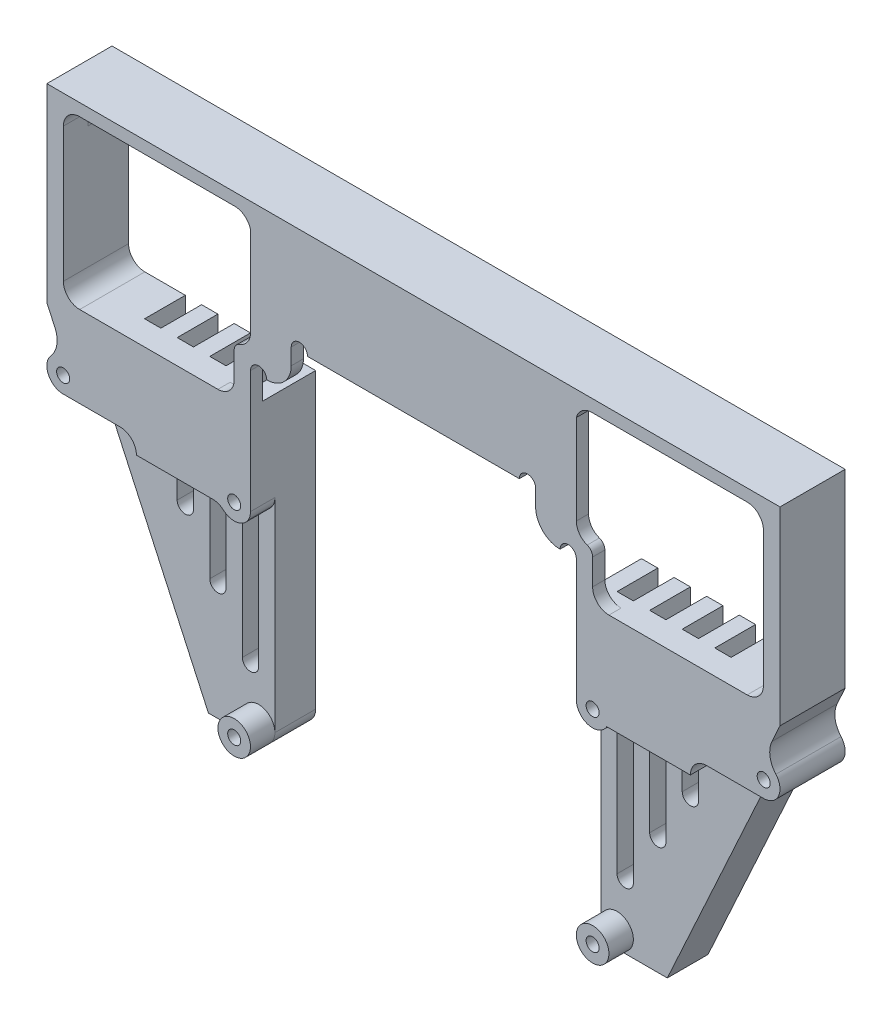
SolidWorks part; units mm, degrees
material "A2017"
ref_plane "正面" through (0, 0, 0) normal (0, 0, 1) x (1, 0, 0)
ref_plane "平面" through (0, 0, 0) normal (0, 1, 0) x (1, 0, 0)
ref_plane "右側面" through (0, 0, 0) normal (1, 0, 0) x (0, 0, -1)
sketch "ｽｹｯﾁ2" plane through (0, 0, 0) normal (0, 0, 1) x (1, 0, 0)
  line L0 (45, -77) -> (-45, -77)
  line L1 (-45, -77) -> (-45, -100.2724)
  line L2 (40.4547, -110.1895) -> (28.1283, -137.0833) construction
  line L3 (57.5, -85) -> (32.6737, -139.1665) construction
  line L4 (23.583, -145) -> (-23.583, -145) construction
  line L5 (-32.6737, -139.1665) -> (-57.5, -85) construction
  line L6 (45, -112.2727) -> (32.6737, -139.1665) construction
  line L7 (23.583, -145) -> (-23.583, -145) construction
  line L8 (-32.6737, -139.1665) -> (-45, -112.2727) construction
  line L9 (45, -77) -> (45, -100.2724)
  line L10 (45, -100.2724) -> (28.1665, -137)
  line L11 (-20, -80) -> (20, -80)
  line L12 (-28.1665, -137) -> (-45, -100.2724)
  line L13 (-28.1283, -137.0833) -> (-40.4547, -110.1895) construction
  line L15 (-20, -135) -> (-20, -80)
  line L19 (22, -137) -> (28.1665, -137)
  line L20 (-22, -137) -> (-28.1665, -137)
  line L22 (23.583, -140) -> (-23.583, -140) construction
  line L23 (20, -80) -> (20, -135.0066)
  line L24 (-43, -137) -> (-22, -137) construction
  line L25 (-20, -135) -> (-20, -79) construction
  line L26 (-45, -79) -> (-45, -135) construction
  line L27 (43, -77) -> (22, -77) construction
  line L28 (45, -135) -> (45, -79) construction
  line L29 (22, -137) -> (43, -137) construction
  line L30 (20, -79) -> (20, -135) construction
  arc A0 (23.583, -145) -> (32.6737, -139.1665) centre (23.583, -135) ccw construction
  arc A1 (-32.6737, -139.1665) -> (-23.583, -145) centre (-23.583, -135) ccw construction
  arc A2 (23.583, -145) -> (32.6737, -139.1665) centre (23.583, -135) ccw construction
  arc A3 (-32.6737, -139.1665) -> (-23.583, -145) centre (-23.583, -135) ccw construction
  arc A4 (-21.8257, -136.9924) -> (-20, -135) centre (-22, -135) ccw construction
  arc A5 (20.0076, -135.1743) -> (22, -137) centre (22, -135) ccw construction
  arc A8 (20, -135.0066) -> (22, -137) centre (22, -135) ccw
  arc A9 (-22, -137) -> (-20, -135) centre (-22, -135) ccw
  arc A10 (-28.1283, -137.0833) -> (-23.583, -140) centre (-23.583, -135) ccw construction
  arc A11 (23.583, -140) -> (28.1283, -137.0833) centre (23.583, -135) ccw construction
  dimension "D1" = 5
  dimension "D2" = 3
extrude "ﾎﾞｽ - 押し出し1" add sketch "ｽｹｯﾁ2" along normal blind 5
sketch "ｽｹｯﾁ3" plane through (0, 0, 5) normal (0, 0, 1) x (1, 0, 0)
  circle A0 centre (-43, -107) radius 2
  circle A1 centre (43, -107) radius 2
  circle A2 centre (43, -107) radius 1.25 construction
  dimension "D1" = 4
extrude "ﾎﾞｽ - 押し出し2" add sketch "ｽｹｯﾁ3" against normal up to surface (5 mm away) up to face at (0.0002, -111.1149, 0)
fillet "ﾌｨﾚｯﾄ1" radius 3 4 edges at (-42.8299, -105.0073, 2.5) (-41.3794, -108.172, 2.5) (41.3794, -108.172, 2.5) (42.8299, -105.0073, 2.5)
sketch "ｽｹｯﾁ4" plane through (0, 0, 5) normal (0, 0, 1) x (1, 0, 0)
  circle A0 centre (-43, -107) radius 2
  circle A1 centre (-22, -110) radius 2
  circle A2 centre (-22, -135) radius 2
  circle A3 centre (22, -135) radius 2
  circle A4 centre (22, -110) radius 2
  circle A5 centre (43, -107) radius 2
  dimension "D1" = 4
extrude "ﾎﾞｽ - 押し出し3" add sketch "ｽｹｯﾁ4" along normal blind 3
sketch "ｽｹｯﾁ5" plane through (0, 0, 5) normal (0, 0, 1) x (1, 0, 0)
  line L0 (20, -80) -> (20, -110) construction
  line L1 (20, -98.9998) -> (42.9701, -98.9998)
  line L2 (20, -98.9998) -> (20, -108.9998)
  line L3 (34, -108.9998) -> (42.9701, -108.9998)
  line L4 (42.9701, -98.9998) -> (42.9701, -108.9998)
  line L5 (20, -110) -> (20, -135) construction
  line L6 (20, -110.9998) -> (34, -110.9998)
  line L7 (20, -110.9998) -> (20, -108.9998)
  line L8 (0, -77) -> (0, -134.0805) construction
  line L9 (34, -110.9998) -> (34, -108.9998)
  line L10 (45, -77) -> (-45, -77) construction
  line L11 (-34, -110.9998) -> (-34, -108.9998)
  line L12 (-20, -110.9998) -> (-20, -108.9998)
  line L13 (-20, -110.9998) -> (-34, -110.9998)
  line L14 (-42.9701, -98.9998) -> (-42.9701, -108.9998)
  line L15 (-34, -108.9998) -> (-42.9701, -108.9998)
  line L16 (-20, -98.9998) -> (-20, -108.9998)
  line L17 (-20, -98.9998) -> (-42.9701, -98.9998)
  circle A0 centre (43, -107) radius 2 construction
  arc A1 (42.9701, -108.9998) -> (40.198, -110.7495) centre (42.9252, -111.9994) ccw construction
  dimension "D1" = 10
  dimension "D2" = 14
  dimension "D3" = 2
extrude "ﾎﾞｽ - 押し出し4" add sketch "ｽｹｯﾁ5" along normal up to surface (3 mm away) up to face at (24, -110, 8)
sketch "ｽｹｯﾁ6" plane through (0, 0, 8) normal (0, 0, 1) x (1, 0, 0)
  line L0 (0, -77) -> (0, -111.4657) construction
  line L1 (42.9701, -98.9998) -> (37.9701, -98.9998)
  line L2 (42.9701, -98.9998) -> (42.9701, -103.9998)
  line L3 (42.9701, -103.9998) -> (37.9701, -103.9998)
  line L4 (37.9701, -98.9998) -> (37.9701, -103.9998)
  line L5 (45, -77) -> (-45, -77) construction
  line L6 (-37.9701, -98.9998) -> (-37.9701, -103.9998)
  line L7 (-42.9701, -103.9998) -> (-37.9701, -103.9998)
  line L8 (-42.9701, -98.9998) -> (-42.9701, -103.9998)
  line L9 (-42.9701, -98.9998) -> (-37.9701, -98.9998)
  dimension "D1" = 5
  dimension "D2" = 5
extrude "ｶｯﾄ - 押し出し1" cut sketch "ｽｹｯﾁ6" against normal up to surface (3 mm away) up to face at (0, -96.0349, 5)
sketch "ｽｹｯﾁ7" plane through (0, 0, 5) normal (0, 0, 1) x (1, 0, 0)
  line L0 (45, -100.2724) -> (45, -77) construction
  line L1 (44.0112, -102.4297) -> (45, -100.2724) construction
  line L2 (45, -100.2724) -> (45, -77)
  line L3 (44.0112, -102.4297) -> (45, -100.2724)
  line L4 (-45, -77) -> (-45, -100.2724) construction
  line L5 (-45, -100.2724) -> (-44.0112, -102.4297) construction
  line L6 (-45, -77) -> (-45, -100.2724)
  line L7 (-45, -100.2724) -> (-44.0112, -102.4297)
  line L8 (45, -77) -> (-45, -77) construction
  line L9 (45, -77) -> (-45, -77)
  line L10 (42.9701, -105.0002) -> (42.9701, -80)
  line L11 (42.9701, -80) -> (-42.9701, -80)
  line L12 (-42.9701, -80) -> (-42.9701, -105.0002)
  arc A0 (44.0112, -102.4297) -> (44.4954, -105.6719) centre (46.7384, -103.6797) ccw construction
  arc A1 (44.0112, -102.4297) -> (44.4954, -105.6719) centre (46.7384, -103.6797) ccw
  arc A2 (-44.4954, -105.6719) -> (-44.0112, -102.4297) centre (-46.7384, -103.6797) ccw construction
  arc A3 (-44.4954, -105.6719) -> (-44.0112, -102.4297) centre (-46.7384, -103.6797) ccw
  arc A5 (42.9701, -108.9998) -> (42.9701, -105.0002) centre (43, -107) ccw construction
  arc A6 (-42.9701, -105.0002) -> (-44.4954, -105.6719) centre (-43, -107) ccw construction
  arc A8 (44.4954, -105.6719) -> (42.9701, -105.0002) centre (43, -107) ccw
  arc A9 (-42.9701, -105.0002) -> (-44.4954, -105.6719) centre (-43, -107) ccw
extrude "ﾎﾞｽ - 押し出し5" add sketch "ｽｹｯﾁ7" along normal up to surface (3 mm away) up to face at (32.6255, -106.7271, 8)
sketch "ｽｹｯﾁ8" plane through (0, 0, 5) normal (0, 0, 1) x (1, 0, 0)
  line L0 (42.9701, -103.9998) -> (42.9701, -80) construction
  line L1 (42.9701, -80) -> (20, -80) construction
  line L2 (20, -80) -> (20, -98.9998) construction
  line L3 (20, -98.9998) -> (37.9701, -98.9998) construction
  line L4 (37.9701, -98.9998) -> (37.9701, -103.9998) construction
  line L5 (37.9701, -103.9998) -> (42.9701, -103.9998) construction
  line L6 (-20, -80) -> (-42.9701, -80) construction
  line L7 (-42.9701, -80) -> (-42.9701, -103.9998) construction
  line L8 (-42.9701, -103.9998) -> (-37.9701, -103.9998) construction
  line L9 (-37.9701, -103.9998) -> (-37.9701, -98.9998) construction
  line L10 (-37.9701, -98.9998) -> (-20, -98.9998) construction
  line L11 (-20, -98.9998) -> (-20, -80) construction
  line L12 (42.9701, -103.9998) -> (42.9701, -80)
  line L13 (42.9701, -80) -> (20, -80)
  line L14 (20, -80) -> (20, -98.9998)
  line L15 (20, -98.9998) -> (37.9701, -98.9998)
  line L16 (37.9701, -98.9998) -> (37.9701, -103.9998)
  line L17 (37.9701, -103.9998) -> (42.9701, -103.9998)
  line L18 (-20, -80) -> (-42.9701, -80)
  line L19 (-42.9701, -80) -> (-42.9701, -103.9998)
  line L20 (-42.9701, -103.9998) -> (-37.9701, -103.9998)
  line L21 (-37.9701, -103.9998) -> (-37.9701, -98.9998)
  line L22 (-37.9701, -98.9998) -> (-20, -98.9998)
  line L23 (-20, -98.9998) -> (-20, -80)
extrude "ｶｯﾄ - 押し出し2" cut sketch "ｽｹｯﾁ8" against normal through all
fillet "ﾌｨﾚｯﾄ2" radius 2 6 edges at (-42.9701, -103.9998, 4) (-37.9701, -103.9998, 4) (37.9701, -103.9998, 4) (42.9701, -103.9998, 4) (42.9701, -80, 4) (-42.9701, -80, 4)
sketch "ｽｹｯﾁ9" plane through (0, 0, 8) normal (0, 0, 1) x (1, 0, 0)
  line L0 (20, -77) -> (20, -82.5) construction
  line L1 (42.9701, -82) -> (20, -82)
  line L2 (42.9701, -82) -> (42.9701, -78.5)
  line L3 (42.9701, -78.5) -> (20, -78.5)
  line L4 (20, -82) -> (20, -78.5)
  line L5 (45, -77) -> (-45, -77) construction
  line L6 (0, -77) -> (0, -137.6393) construction
  line L7 (-20, -82) -> (-20, -78.5)
  line L8 (-42.9701, -78.5) -> (-20, -78.5)
  line L9 (-42.9701, -82) -> (-42.9701, -78.5)
  line L10 (-42.9701, -82) -> (-20, -82)
  dimension "D1" = 1.5
extrude "ｶｯﾄ - 押し出し3" cut sketch "ｽｹｯﾁ9" against normal blind 3
fillet "ﾌｨﾚｯﾄ3" radius 2 4 edges at (42.9701, -78.5, 6.5) (20, -78.5, 6.5) (-20, -78.5, 6.5) (-42.9701, -78.5, 6.5)
fillet "ﾌｨﾚｯﾄ4" radius 2 5 edges at (34, -108.9998, 6.5) (-20, -110.9998, 6.5) (20, -110.9998, 6.5) (-23.7322, -110.9998, 6.5) (-34, -108.9998, 6.5)
sketch "ｽｹｯﾁ10" plane through (0, 0, 0) normal (0, 0, -1) x (-1, 0, 0)
  line L0 (-23, -98.9998) -> (-23, -128.9998) construction
  line L1 (-20, -98.9998) -> (-37.9701, -98.9998) construction
  line L2 (-22, -98.9998) -> (-22, -128.9998)
  line L3 (-24, -98.9998) -> (-24, -128.9998)
  line L4 (-20, -98.9998) -> (-20, -135.0066) construction
  line L5 (-27, -98.9998) -> (-27, -122.6356) construction
  line L6 (-26, -98.9998) -> (-26, -122.6356)
  line L7 (-28, -98.9998) -> (-28, -122.6356)
  line L8 (-23, -128.9998) -> (-39.9701, -101.9998) construction
  line L9 (-31, -98.9998) -> (-31, -116.2715) construction
  line L10 (-30, -98.9998) -> (-30, -116.2715)
  line L11 (-32, -98.9998) -> (-32, -116.2715)
  line L12 (-35, -98.9998) -> (-35, -109.9073) construction
  line L13 (-34, -98.9998) -> (-34, -109.9073)
  line L14 (-36, -98.9998) -> (-36, -109.9073)
  line L15 (0, -77) -> (0, -136.588) construction
  line L16 (-45, -77) -> (45, -77) construction
  line L17 (23, -98.9998) -> (23, -128.9998) construction
  line L18 (22, -98.9998) -> (22, -128.9998)
  line L19 (24, -98.9998) -> (24, -128.9998)
  line L20 (27, -98.9998) -> (27, -122.6356) construction
  line L21 (26, -98.9998) -> (26, -122.6356)
  line L22 (28, -98.9998) -> (28, -122.6356)
  line L23 (31, -98.9998) -> (31, -116.2715) construction
  line L24 (30, -98.9998) -> (30, -116.2715)
  line L25 (32, -98.9998) -> (32, -116.2715)
  line L26 (35, -98.9998) -> (35, -109.9073) construction
  line L27 (34, -98.9998) -> (34, -109.9073)
  line L28 (36, -98.9998) -> (36, -109.9073)
  line L29 (23, -128.9998) -> (39.9701, -101.9998) construction
  arc A0 (-22, -98.9998) -> (-24, -98.9998) centre (-23, -98.9998) ccw
  arc A1 (-24, -128.9998) -> (-22, -128.9998) centre (-23, -128.9998) ccw
  arc A2 (-26, -98.9998) -> (-28, -98.9998) centre (-27, -98.9998) ccw
  arc A3 (-28, -122.6356) -> (-26, -122.6356) centre (-27, -122.6356) ccw
  arc A4 (-30, -98.9998) -> (-32, -98.9998) centre (-31, -98.9998) ccw
  arc A5 (-32, -116.2715) -> (-30, -116.2715) centre (-31, -116.2715) ccw
  arc A6 (-34, -98.9998) -> (-36, -98.9998) centre (-35, -98.9998) ccw
  arc A7 (-36, -109.9073) -> (-34, -109.9073) centre (-35, -109.9073) ccw
  arc A8 (22, -98.9998) -> (24, -98.9998) centre (23, -98.9998) cw
  arc A9 (24, -128.9998) -> (22, -128.9998) centre (23, -128.9998) cw
  arc A10 (26, -98.9998) -> (28, -98.9998) centre (27, -98.9998) cw
  arc A11 (28, -122.6356) -> (26, -122.6356) centre (27, -122.6356) cw
  arc A12 (30, -98.9998) -> (32, -98.9998) centre (31, -98.9998) cw
  arc A13 (32, -116.2715) -> (30, -116.2715) centre (31, -116.2715) cw
  arc A14 (34, -98.9998) -> (36, -98.9998) centre (35, -98.9998) cw
  arc A15 (36, -109.9073) -> (34, -109.9073) centre (35, -109.9073) cw
  point P4 (-23, -113.9998)
  point P13 (-27, -110.8177)
  point P23 (-31, -107.6356)
  point P30 (-35, -104.4536)
  point P42 (23, -113.9998)
  point P49 (27, -110.8177)
  point P56 (31, -107.6356)
  point P63 (35, -104.4536)
  dimension "D1" = 2
  dimension "D2" = 2
  dimension "D3" = 30
  dimension "D4" = 2
  dimension "D5" = 2
  dimension "D6" = 2
extrude "ｶｯﾄ - 押し出し4" cut sketch "ｽｹｯﾁ10" against normal blind 5
hole_wizard "M2 ねじ穴1" positions "ｽｹｯﾁ11" profile "ｽｹｯﾁ13" tap size "M2" standard "JIS" end condition through all
sketch "ｽｹｯﾁ11" plane through (0, 0, 8) normal (0, 0, 1) x (1, 0, 0)
  point P0 (43, -107)
  point P3 (22, -110)
  point P6 (22, -135)
  point P9 (-22, -110)
  point P12 (-22, -135)
  point P15 (-43, -107)
sketch "ｽｹｯﾁ13" plane through (43, -107, 8) normal (1, 0, 0) x (0, -1, 0)
  line L0 (0, 0) -> (0, 8)
  line L1 (0, 8) -> (0.8, 8)
  line L2 (0.8, 8) -> (0.8, 0)
  line L5 (0.8, 0) -> (0, 0)
  line L11 (0, -6.35) -> (0, 107.95) construction
  dimension "次ｻｰﾌｪｽまでのねじ下穴ﾄﾞﾘﾙ直径" = 1.6
  dimension "次ｻｰﾌｪｽまでのねじ下穴ﾄﾞﾘﾙの深さ" = 8
cosmetic thread "穴のねじ山1" parameters "D2"=2
cosmetic thread "穴のねじ山2" parameters "D2"=2
cosmetic thread "穴のねじ山3" parameters "D2"=2
cosmetic thread "穴のねじ山4" parameters "D2"=2
cosmetic thread "穴のねじ山5" parameters "D2"=2
cosmetic thread "穴のねじ山6" parameters "D2"=2
sketch "ｽｹｯﾁ14" plane through (0, 0, 8) normal (0, 0, 1) x (1, 0, 0)
  line L0 (-42.9701, -101.9998) -> (-42.9701, -80.5) construction
  line L1 (-40.9701, -103.9998) -> (-39.9701, -103.9998) construction
  line L2 (-37.9701, -101.9998) -> (-37.9701, -98.9998) construction
  line L3 (42.9701, -80.5) -> (42.9701, -101.9998) construction
  line L4 (39.9701, -103.9998) -> (40.9701, -103.9998) construction
  line L5 (37.9701, -98.9998) -> (37.9701, -101.9998) construction
  line L6 (-42.9701, -101.9998) -> (-42.9701, -98.9998)
  line L7 (-40.9701, -103.9998) -> (-39.9701, -103.9998)
  line L8 (-37.9701, -101.9998) -> (-37.9701, -98.9998)
  line L9 (42.9701, -98.9998) -> (42.9701, -101.9998)
  line L10 (39.9701, -103.9998) -> (40.9701, -103.9998)
  line L11 (37.9701, -98.9998) -> (37.9701, -101.9998)
  line L12 (37.9701, -98.9998) -> (42.9701, -98.9998)
  line L13 (-37.9701, -98.9998) -> (-42.9701, -98.9998)
  arc A0 (-42.9701, -101.9998) -> (-40.9701, -103.9998) centre (-40.9701, -101.9998) ccw construction
  arc A1 (-39.9701, -103.9998) -> (-37.9701, -101.9998) centre (-39.9701, -101.9998) ccw construction
  arc A2 (40.9701, -103.9998) -> (42.9701, -101.9998) centre (40.9701, -101.9998) ccw construction
  arc A3 (37.9701, -101.9998) -> (39.9701, -103.9998) centre (39.9701, -101.9998) ccw construction
  arc A4 (-42.9701, -101.9998) -> (-40.9701, -103.9998) centre (-40.9701, -101.9998) ccw
  arc A5 (-39.9701, -103.9998) -> (-37.9701, -101.9998) centre (-39.9701, -101.9998) ccw
  arc A6 (40.9701, -103.9998) -> (42.9701, -101.9998) centre (40.9701, -101.9998) ccw
  arc A7 (37.9701, -101.9998) -> (39.9701, -103.9998) centre (39.9701, -101.9998) ccw
extrude "ﾎﾞｽ - 押し出し6" add sketch "ｽｹｯﾁ14" against normal up to surface (8 mm away) up to face at (43.8, -107, 0)
fillet "ﾌｨﾚｯﾄ5" radius 2 2 edges at (-42.9701, -98.9998, 4) (42.9701, -98.9998, 4)
sketch "ｽｹｯﾁ15" plane through (0, 0, 8) normal (0, 0, 1) x (1, 0, 0)
  line L0 (-14.5, -90) -> (14.5, -90) construction
  line L1 (-20, -80) -> (20, -80)
  line L2 (-20, -80) -> (-20, -90)
  line L3 (-20, -90) -> (20, -90)
  line L4 (20, -80) -> (20, -90)
extrude "ﾎﾞｽ - 押し出し8" add sketch "ｽｹｯﾁ15" against normal blind 1.5
sketch "ｽｹｯﾁ16" plane through (0, 0, 8) normal (0, 0, 1) x (1, 0, 0)
  line L2 (20, -98.9998) -> (20, -95)
  line L3 (20, -95.5) -> (20, -93) construction
  line L4 (20, -95) -> (18, -95)
  line L5 (15, -92) -> (15, -90)
  line L6 (-20, -90) -> (20, -90) construction
  line L11 (20, -135) -> (20, -79) construction
  line L12 (20, -98.9998) -> (22, -98.9998) construction
  line L13 (20, -98.9998) -> (22, -98.9998)
  line L14 (22, -98.9998) -> (22, -93)
  line L15 (15, -90) -> (20, -90)
  line L16 (22, -93) -> (20, -93)
  line L17 (20, -93) -> (20, -90)
  arc A0 (15, -92) -> (18, -95) centre (18, -92) ccw construction
  arc A1 (15, -92) -> (18, -95) centre (18, -92) ccw
  dimension "D1" = 3
extrude "ﾎﾞｽ - 押し出し9" add sketch "ｽｹｯﾁ16" against normal up to surface (1.5 mm away) up to face at (0, -85, 6.5)
mirror "ﾐﾗｰ1" about plane through (0, 0, 0) normal (1, 0, 0) of "ﾎﾞｽ - 押し出し9"
fillet "ﾌｨﾚｯﾄ7" radius 2 2 edges at (-20, -93, 7.25) (20, -93, 7.25)
fillet "ﾌｨﾚｯﾄ8" radius 1 2 edges at (22, -93, 7.25) (-22, -93, 7.25)
fillet "ﾌｨﾚｯﾄ9" radius 2 2 edges at (22, -98.9998, 7.25) (-22, -98.9998, 7.25)
sketch "ｽｹｯﾁ17" plane through (0, 0, 8) normal (0, 0, 1) x (1, 0, 0)
  line L0 (-18, -95) -> (-20, -95) construction
  line L1 (-15, -90) -> (15, -90) construction
  line L2 (0, -77) -> (0, -99.7898) construction
  line L3 (45, -77) -> (-45, -77) construction
  circle A0 centre (-19, -95) radius 1
  circle A1 centre (-14, -90) radius 1
  circle A2 centre (14, -90) radius 1
  circle A3 centre (19, -95) radius 1
  dimension "D1" = 2
extrude "ｶｯﾄ - 押し出し5" cut sketch "ｽｹｯﾁ17" against normal through all
